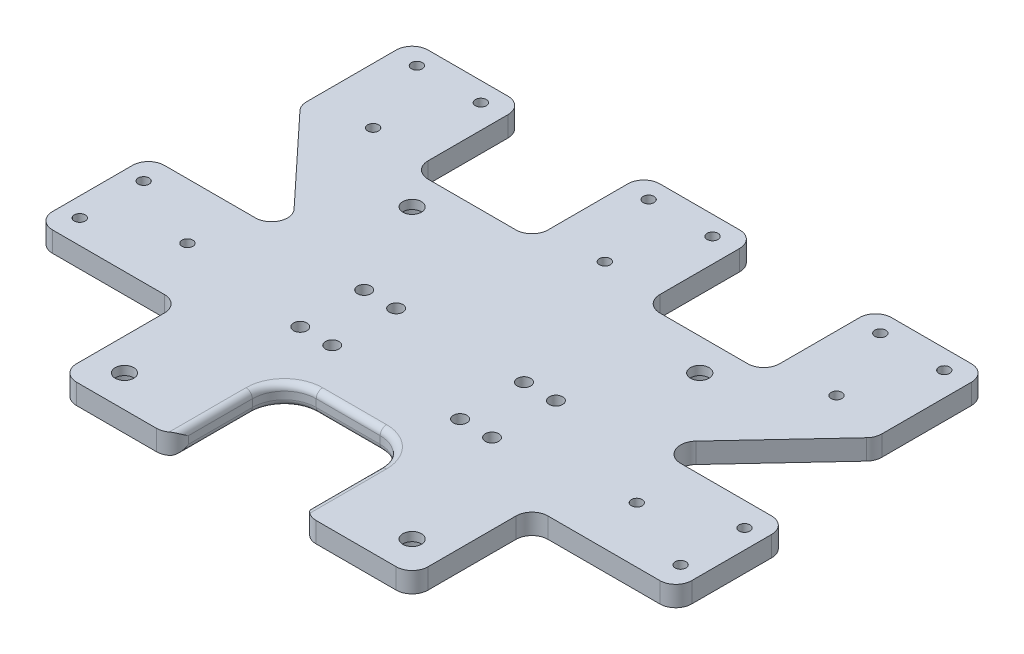
SolidWorks part; units mm, degrees
ref_plane "Front Plane" through (0, 0, 0) normal (0, 0, 1) x (1, 0, 0)
ref_plane "Top Plane" through (0, 0, 0) normal (0, 1, 0) x (1, 0, 0)
ref_plane "Right Plane" through (0, 0, 0) normal (1, 0, 0) x (0, 0, -1)
sketch "Sketch1" plane through (0, 0, 0) normal (0, 1, 0) x (1, 0, 0)
  line L0 (55, -55) -> (-55, -55)
  line L5 (17.5, 55) -> (17.5, 90)
  line L6 (55, 55) -> (17.5, 55)
  line L7 (-55, -55) -> (-55, -17.5)
  line L8 (-55, -17.5) -> (-100, -17.5)
  line L9 (-100, -17.5) -> (-100, 17.5)
  line L10 (-100, 17.5) -> (-55, 17.5)
  line L11 (-55, 17.5) -> (-55, 55) construction
  line L12 (-55, 55) -> (-17.5, 55)
  line L13 (-17.5, 55) -> (-17.5, 90)
  line L14 (-17.5, 90) -> (17.5, 90)
  line L15 (0, 90) -> (0, -55) construction
  line L16 (55, 17.5) -> (55, 55) construction
  line L17 (100, 17.5) -> (55, 17.5)
  line L18 (100, -17.5) -> (100, 17.5)
  line L19 (55, -17.5) -> (100, -17.5)
  line L20 (55, -55) -> (55, -17.5)
  line L21 (-55, 55) -> (-55, 90)
  line L22 (-55, 90) -> (-90, 90)
  line L23 (-90, 90) -> (-90, 55)
  line L24 (-90, 55) -> (-55, 17.5)
  line L25 (90, 55) -> (55, 17.5)
  line L26 (90, 90) -> (90, 55)
  line L27 (55, 55) -> (55, 90)
  line L28 (55, 90) -> (90, 90)
  point P0 (0, 0)
  dimension "D1" = 55
  dimension "D2" = 55
  dimension "D3" = 55
  dimension "D4" = 100
  dimension "D5" = 35
  dimension "D6" = 17.5
  dimension "D7" = 90
  dimension "D8" = 17.5
  dimension "D9" = 35
extrude "Boss-Extrude1" add sketch "Sketch1" along normal blind 6.35
sketch "Sketch4" plane through (0, 6.35, 0) normal (0, 1, 0) x (1, 0, 0)
  line L0 (-20, -55) -> (-20, -20)
  line L1 (-55, -55) -> (55, -55) construction
  line L2 (-20, -20) -> (20, -20)
  line L3 (20, -20) -> (20, -55)
  line L4 (20, -55) -> (-20, -55)
  point P4 (0, -55)
  point P8 (0, -55)
  dimension "D1" = 40
  dimension "D2" = 35
extrude "Cut-Extrude1" cut sketch "Sketch4" against normal through all
fillet "Fillet1" radius 5 24 edges at (17.5, 3.175, -55) (17.5, 3.175, -90) (100, 3.175, -17.5) (55, 3.175, 17.5) (100, 3.175, 17.5) (55, 3.175, 55) (-55, 3.175, 55) (-100, 3.175, 17.5) (-100, 3.175, -17.5) (-17.5, 3.175, -55) (-17.5, 3.175, -90) (-55, 3.175, 17.5) (20, 3.175, 55) (-20, 3.175, 55) (-55, 3.175, -90) (-90, 3.175, -90) (55, 3.175, -90) (90, 3.175, -90) (55, 3.175, -17.5) (90, 3.175, -55) (55, 3.175, -55) (-55, 3.175, -55) (-90, 3.175, -55) (-55, 3.175, -17.5)
hole_wizard "CBORE for M5 Hex Head Bolt1" positions "Sketch2" profile "Sketch3" counterbore size "M5" standard "ANSI Metric" end condition through all
sketch "Sketch2" plane through (0, 0, 0) normal (0, 1, 0) x (1, 0, 0)
  line L0 (0, 76.3058) -> (0, -76.3058) construction
  line L4 (60, 0) -> (-60, 0) construction
  point P15 (-45, 45)
  point P19 (45, 45)
  point P22 (45, -45)
  point P23 (-45, -45)
  point P30 (0, 0)
  point P31 (0, 0)
  dimension "D1" = 45
  dimension "D2" = 45
sketch "Sketch3" plane through (-45, 0, 45) normal (1, 0, 0) x (0, 0, -1)
  line L0 (0, 0) -> (0, 6.35)
  line L1 (0, 6.35) -> (2.9, 6.35)
  line L3 (2.9, 6.35) -> (2.9, 3.58)
  line L4 (2.9, 3.58) -> (6.12, 3.58)
  line L5 (6.12, 3.58) -> (6.12, 0)
  line L7 (6.12, 0) -> (0, 0)
  line L11 (0, -6.35) -> (0, 107.95) construction
  dimension "Thru Hole Dia." = 5.8
  dimension "Thru Hole Depth" = 6.35
  dimension "C'Bore Dia." = 12.24
  dimension "C'Bore Depth" = 3.58
sketch "Sketch5" plane through (0, 0, 0) normal (0, 1, 0) x (1, 0, 0)
  line L0 (-101.5196, 0.1307) -> (-95.4419, 34.599)
  line L1 (-95.4419, 34.599) -> (-17.5, 90)
  line L2 (-17.5, 90) -> (17.5, 90)
  line L3 (17.5, 90) -> (95.4419, 34.599)
  line L4 (95.4419, 34.599) -> (101.5196, 0.1307)
  line L5 (101.5196, 0.1307) -> (46.553, -47.5537)
  line L6 (40, -50) -> (15, -50)
  line L7 (15, -50) -> (15, -15)
  line L8 (15, -15) -> (-15, -15)
  line L9 (-15, -15) -> (-15, -50)
  line L10 (-15, -50) -> (-40, -50)
  line L11 (-46.553, -47.5537) -> (-101.5196, 0.1307)
  line L12 (-55, 0) -> (55, 0) construction
  line L13 (0, 0) -> (0, 180) construction
  line L14 (-98.4808, 17.3648) -> (0, 0) construction
  arc A0 (-46.553, -47.5537) -> (-40, -50) centre (-40, -40) ccw
  arc A2 (46.553, -47.5537) -> (40, -50) centre (40, -40) cw
  point P25 (0, 90)
  dimension "D7" = 35
  dimension "D1" = 50
  dimension "D2" = 90
  dimension "D3" = 35
  dimension "D4" = 80
  dimension "D5" = 100
  dimension "D6" = 30
  dimension "D8" = 15
  dimension "D9" = 40
  dimension "D10" = 40
extrude "Boss-Extrude2" [suppressed] add sketch "Sketch5" along normal blind 6.35 separate body
fillet "Fillet2" radius 10 2 edges at (20, 3.175, 20) (-20, 3.175, 20)
fillet "Fillet3" radius 2 6 edges at (20, 6.35, 40) (0, 6.35, 20) (-20, 6.35, 40) (-20, 0, 40) (20, 0, 40) (0, 0, 20)
hole_wizard "CBORE for M3 SHCS1" positions "Sketch6" profile "Sketch7" counterbore size "M3" standard "ANSI Metric" end condition through all
sketch "Sketch6" plane through (0, 0, 0) normal (0, -1, 0) x (-1, 0, 0)
  line L0 (-94, -10) -> (-94, 10) construction
  line L3 (-70.3, 0) -> (-94, 0) construction
  line L7 (94, -10) -> (94, 10) construction
  line L9 (94, 0) -> (70.3, 0) construction
  line L17 (0, 0) -> (0, 84) construction
  line L18 (-10, 84) -> (10, 84)
  line L20 (-62.5, 84) -> (-82.5, 84)
  line L22 (-82.5, 84) -> (-90, 84) construction
  line L23 (-90, 56.9708) -> (-90, 85) construction
  line L25 (-62.5, 84) -> (-55, 84) construction
  line L26 (-55, 85) -> (-55, 60) construction
  point P0 (10, 84)
  point P2 (-10, 84)
  point P5 (0, 60.3)
  point P8 (-94, 10)
  point P10 (-94, -10)
  point P13 (-70.3, 0)
  point P16 (94, -10)
  point P19 (94, 10)
  point P22 (70.3, 0)
  point P97 (-82.5, 84)
  point P99 (-62.5, 84)
  point P101 (-72.5, 60.3)
  point P127 (-72.5, 84)
  point P128 (72.5, 60.3)
  point P129 (82.5, 84)
  point P130 (62.5, 84)
  point P132 (0, 0)
  point P133 (0, 0)
  point P134 (0, 0)
  point P135 (0, 0)
  point P136 (0, 0)
  point P137 (0, 0)
  point P138 (0, 0)
  point P139 (0, 0)
  point P140 (0, 0)
  point P141 (0, 0)
  point P142 (0, 0)
  point P143 (0, 84)
sketch "Sketch7" plane through (-10, 0, -84) normal (1, 0, 0) x (0, 0, -1)
  line L0 (0, 0) -> (0, 6.35)
  line L1 (0, 6.35) -> (1.7, 6.35)
  line L3 (1.7, 6.35) -> (1.7, 3)
  line L4 (1.7, 3) -> (3.25, 3)
  line L5 (3.25, 3) -> (3.25, 0)
  line L7 (3.25, 0) -> (0, 0)
  line L11 (0, -6.35) -> (0, 107.95) construction
  dimension "Thru Hole Dia." = 3.4
  dimension "Thru Hole Depth" = 6.35
  dimension "C'Bore Dia." = 6.5
  dimension "C'Bore Depth" = 3
hole_wizard "M5x0.8 Tapped Hole1" positions "Sketch10" profile "Sketch11" tap size "M5x0.8" standard "ANSI Metric" end condition through all
sketch "Sketch10" plane through (0, 0, 0) normal (0, -1, 0) x (-1, 0, 0)
  point P0 (-20, 15)
  point P2 (20, 15)
  point P4 (20, -5)
  point P6 (-20, -5)
  point P10 (-30, 15)
  point P12 (-30, -5)
  point P14 (30, 15)
  point P16 (30, -5)
  dimension "D1" = 40
  dimension "D2" = 20
  dimension "D3" = 15
  dimension "D4" = 20
  dimension "D5" = 60
  dimension "D6" = 30
sketch "Sketch11" plane through (20, 0, -15) normal (1, 0, 0) x (0, 0, -1)
  line L0 (0, 0) -> (0, 6.35)
  line L1 (0, 6.35) -> (2.1, 6.35)
  line L2 (2.1, 6.35) -> (2.1, 0)
  line L5 (2.1, 0) -> (0, 0)
  line L11 (0, -6.35) -> (0, 107.95) construction
  dimension "Thru Tap Drill Dia." = 4.2
  dimension "Thru Tap Drill Depth" = 6.35
cosmetic thread "Hole Thread1" parameters "D2"=5
cosmetic thread "Hole Thread2" parameters "D2"=5
cosmetic thread "Hole Thread3" parameters "D2"=5
cosmetic thread "Hole Thread4" parameters "D2"=5
cosmetic thread "Hole Thread5" parameters "D2"=5
cosmetic thread "Hole Thread6" parameters "D2"=5
cosmetic thread "Hole Thread7" parameters "D2"=5
cosmetic thread "Hole Thread8" parameters "D2"=5
